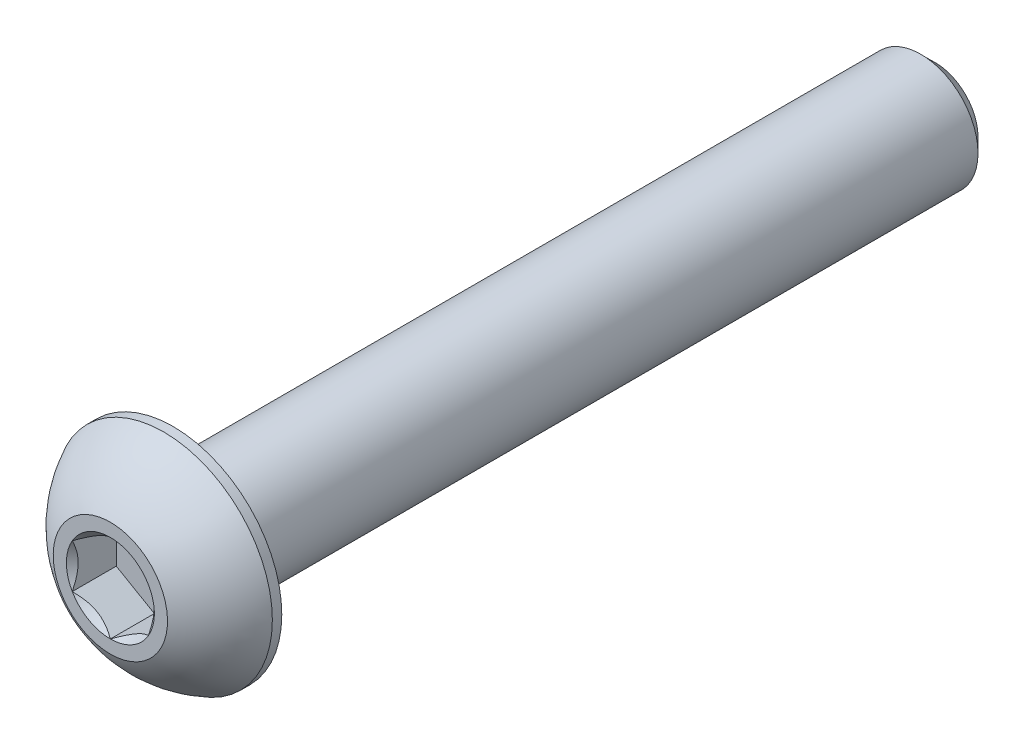
SolidWorks part; units mm, degrees
ref_plane "Front" through (0, 0, 0) normal (0, 0, 1) x (1, 0, 0)
ref_plane "Top" through (0, 0, 0) normal (0, 1, 0) x (1, 0, 0)
ref_plane "Right" through (0, 0, 0) normal (1, 0, 0) x (0, 0, -1)
sketch "Sketch1" plane through (0, 0, 0) normal (1, 0, 0) x (0, 0, -1)
  line L2 (1.65, 1.5) -> (21.65, 1.5)
  line L3 (21.65, 1.5) -> (21.65, 0)
  line L4 (21.65, 0) -> (1.65, 0)
  line L6 (1.4025, 2.85) -> (1.65, 2.85) construction
  line L7 (21.65, 1.5) -> (21.65, -1.5) construction
  line L8 (0, 0) -> (1.65, 0) construction
  line L9 (1.65, 2.85) -> (1.65, -2.85) construction
  line L11 (1.65, 1.5) -> (1.65, 0)
  line L13 (0, 1) -> (0, -1) construction
  line L14 (0, 1) -> (0, 1.5) construction
  arc A3 (0, 1.5) -> (1.4025, 2.85) centre (2.7948, 0) cw construction
  dimension "D1" = 0.2475
revolve "Revolve1" add sketch "Sketch1" angle 360 mid plane about L4
sketch "Sketch3" plane through (0, 0, -21.65) normal (0, 0, -1) x (-1, 0, 0)
  circle A0 centre (0, 0) radius 1.5
curve "Helix/Spiral1" [suppressed]
chamfer "Chamfer1" distance 0.375 angle 45 1 edges at (0, 1.5, -21.65)
sketch "Sketch7" plane through (0, 0, 0) normal (1, 0, 0) x (0, 0, -1)
  line L6 (1.4025, 2.85) -> (1.65, 2.85) construction
  line L8 (0, 0) -> (1.65, 0) construction
  line L11 (1.65, 2.85) -> (1.65, -2.85) construction
  line L12 (1.4025, 2.85) -> (1.65, 2.85)
  line L13 (0, 0) -> (1.65, 0)
  line L14 (0, 1) -> (0, -1) construction
  line L15 (1.65, 2.85) -> (1.65, 0)
  line L16 (0, 1.5) -> (0, 0)
  arc A2 (1.4025, 2.85) -> (0, 1.5) centre (2.7948, 0) ccw construction
  arc A3 (1.4025, 2.85) -> (0, 1.5) centre (2.7948, 0) ccw
revolve "Revolve2" add sketch "Sketch7" angle 360 mid plane about L13
sketch "Sketch5" plane through (0, 0, 0) normal (0, 0, 1) x (1, 0, 0)
  line L1 (1, -0.5774) -> (1, 0.5774)
  line L2 (1, 0.5774) -> (0, 1.1547)
  line L3 (0, 1.1547) -> (-1, 0.5774)
  line L4 (-1, 0.5774) -> (-1, -0.5774)
  line L5 (-1, -0.5774) -> (0, -1.1547)
  line L6 (0, -1.1547) -> (1, -0.5774)
  circle A0 centre (0, 0) radius 1 construction
extrude "Cut-Extrude2" cut sketch "Sketch5" against normal blind 1.155
sketch "Sketch6" plane through (0, 0, 0) normal (0, 0, 1) x (1, 0, 0)
  circle A0 centre (0, 0) radius 1.1547
extrude "Cut-Extrude3" cut sketch "Sketch6" against normal blind 1.155 draft 45
sketch "Sketch2" plane through (0, 0, 0) normal (1, 0, 0) x (0, 0, -1)
  line L0 (21.275, 1.5) -> (21.7125, 1.5)
  line L1 (21.7125, 1.5) -> (21.525, 1.1752)
  line L2 (21.525, 1.1752) -> (21.4625, 1.1752)
  line L3 (21.4625, 1.1752) -> (21.275, 1.5)
  line L4 (21.3688, 1.3376) -> (21.6188, 1.3376) construction
  dimension "D1" = 60
  dimension "D2" = 0.0625
  dimension "D3" = 0.25
sweep "Cut-Sweep1" [suppressed] cut profiles "Sketch2" path "Helix/Spiral1"
sketch "Sketch10" plane through (0, 0, 0) normal (1, 0, 0) x (0, 0, -1)
  line L0 (21.65, 1.5) -> (21.65, -1.5) construction
  point P0 (20.9, -1.5)
  dimension "D1" = 0.75
ref_axis "Center Axis 1" through (0, 0, -8.1113) along (0, 0, 1)
ref_plane "Contact Plane 1" through (0, 0, -1.65) normal (0, 0, -1) x (-1, 0, 0)
ref_plane "Contact Plane 2" through (0, 0, 0) normal (0, 0, 1) x (1, 0, 0)
equation "\"D3@Helix/Spiral1\" = \"Lg@Sketch1\" + \"D4@Helix/Spiral1\""
equation "\"D2@Sketch2\" = \"D4@Helix/Spiral1\" * .125"
equation "\"D3@Sketch2\" = \"D4@Helix/Spiral1\" * .5"
equation "\"D1@Chamfer1\" = \"D4@Helix/Spiral1\" * .75"
equation "\"D1@Cut-Extrude2\" = \"Head Ht@Sketch1\" * .7"
equation "\"D1@Sketch1\" = \"Head Ht@Sketch1\" * .15"
equation "\"D1@Sketch10\" = \"D4@Helix/Spiral1\" * 1.5"
equation "\"D1@Cut-Extrude3\" = \"D1@Cut-Extrude2\""
